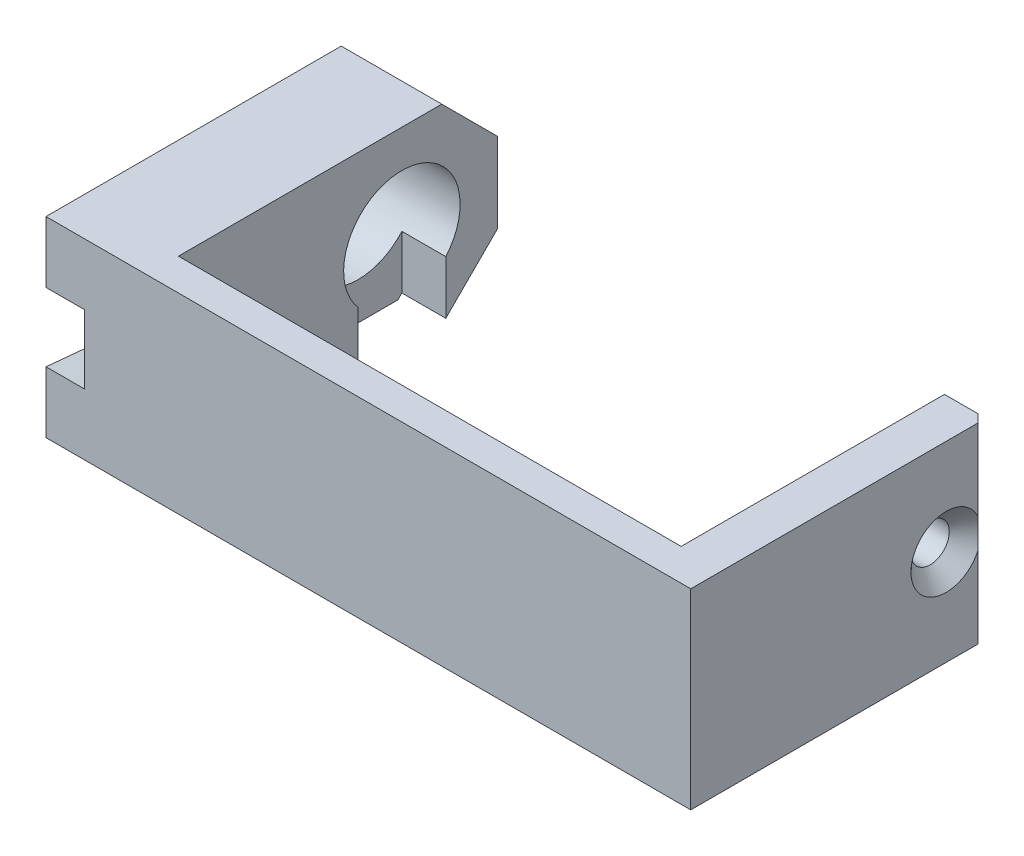
SolidWorks part; units mm, degrees
ref_plane "Front" through (0, 0, 0) normal (0, 0, 1) x (1, 0, 0)
ref_plane "Top" through (0, 0, 0) normal (0, 1, 0) x (1, 0, 0)
ref_plane "Right" through (0, 0, 0) normal (1, 0, 0) x (0, 0, -1)
sketch "Sketch1" plane through (0, 0, 0) normal (0, 0, 1) x (1, 0, 0)
  line L5 (20.2, -6) -> (-20.2, -6)
  line L6 (20.2, -6) -> (20.2, 6)
  line L7 (20.2, 6) -> (-20.2, 6)
  line L8 (-20.2, -6) -> (-20.2, 6)
  line L9 (20.2, -6) -> (-20.2, 6) construction
  line L10 (20.2, 6) -> (-20.2, -6) construction
  point P0 (0, 0)
  dimension "D1" = 40.4
  dimension "D2" = 12
extrude "Boss-Extrude1" add sketch "Sketch1" along normal blind 22 contours L7 L8 L5 L6
sketch "Sketch2" plane through (0, 6, 0) normal (0, 1, 0) x (1, 0, 0)
  line L0 (20.2, 0) -> (-20.2, 0) construction
  line L1 (-13.9, 0) -> (17.6, 0)
  line L2 (-13.9, 0) -> (-13.9, -20)
  line L3 (-13.9, -20) -> (17.6, -20)
  line L4 (17.6, 0) -> (17.6, -20)
  line L5 (-20.2, -22) -> (-20.2, 0) construction
  line L6 (20.2, -22) -> (20.2, 0) construction
  dimension "D1" = 6.3
  dimension "D2" = 31.5
  dimension "D3" = 20
  dimension "D4" = 2.6
extrude "Cut-Extrude1" cut sketch "Sketch2" against normal up to next
sketch "Sketch4" plane through (20.2, 0, 0) normal (1, 0, 0) x (0, 0, -1)
  line L0 (0, -6) -> (0, 6) construction
  circle A0 centre (-6, 0) radius 0.9
  dimension "D1" = 1.8
  dimension "D2" = 6
extrude "Cut-Extrude2" cut sketch "Sketch4" against normal up to next
ref_plane "Plane1" through (0, -36, 0) normal (0, -1, 0) x (-1, 0, 0)
sketch "Sketch5" plane through (-20.2, 0, 0) normal (-1, 0, 0) x (0, 0, 1)
  line L0 (6, 0) -> (22.45, 0) construction
  line L1 (6.3157, 3.3351) -> (22.6196, 1.792) construction
  line L2 (6.3157, -3.3351) -> (22.6196, -1.792) construction
  line L3 (0, -6) -> (0, 6) construction
  line L4 (6.3439, 3.6338) -> (22.6479, 2.0907)
  line L5 (6.3439, -3.6338) -> (22.6479, -2.0907)
  circle A0 centre (6, 0) radius 3.35 construction
  circle A1 centre (22.45, 0) radius 1.8 construction
  arc A2 (6.3157, 3.3351) -> (6.3157, -3.3351) centre (6, 0) ccw construction
  arc A3 (22.6196, 1.792) -> (22.6196, -1.792) centre (22.45, 0) cw construction
  arc A4 (22.6479, 2.0907) -> (22.6479, -2.0907) centre (22.45, 0) cw
  arc A5 (6.3439, 3.6338) -> (6.3439, -3.6338) centre (6, 0) ccw
  point P6 (2.65, 0)
  point P7 (24.25, 0)
  point P13 (0, 0)
  dimension "D1" = 6.7
  dimension "D2" = 3.6
  dimension "D4" = 0.3
  dimension "D3" = 21.6
  dimension "D5" = 6
sketch "Sketch14" plane through (0, 0, 22) normal (0, 0, 1) x (1, 0, 0)
  line L4 (20.2, -6) -> (20.2, 6)
  line L5 (20.2, 6) -> (-20.2, 6)
  line L6 (-20.2, 6) -> (-20.2, -6)
  line L7 (-20.2, -6) -> (20.2, -6)
  line L8 (20.2, -6) -> (20.2, 6)
  line L9 (20.2, 6) -> (-20.2, 6)
  line L10 (-20.2, 6) -> (-20.2, -6)
  line L11 (-20.2, -6) -> (20.2, -6)
  dimension "D1" = 0
chamfer "Chamfer1" distance 3.5 angle 45 4 edges at (-17.05, -6, 0) (-17.05, 6, 0) (18.9, -6, 0) (18.9, 6, 0)
hole_wizard "CSK for M2 Flat Head Machine Screw1" positions "Sketch17" profile "Sketch18" countersink size "M2" standard "ANSI Metric"
sketch "Sketch17" plane through (20.2, 0, 0) normal (1, 0, 0) x (0, 0, -1)
  point P0 (-6, 0)
sketch "Sketch18" plane through (20.2, 0, 6) normal (0, 1, 0) x (0, 0, -1)
  line L0 (0, 0) -> (0, 13.421)
  line L1 (0, 13.421) -> (1.2, 12.7)
  line L2 (1.2, 12.7) -> (1.2, 1)
  line L3 (1.2, 1) -> (2.2, 0)
  line L5 (2.2, 0) -> (0, 0)
  line L6 (-1.2, 1) -> (-2.2, 0) construction
  line L10 (0, 13.421) -> (-1.2, 12.7) construction
  line L11 (0, -6.35) -> (0, 107.95) construction
  dimension "Hole Dia." = 2.4
  dimension "Hole Depth" = 12.7
  dimension "Near C'Sink Dia." = 4.4
  dimension "Near C'Sink Angle" = 90
  dimension "Drill Angle" = 118
chamfer "Chamfer2" distance 4 angle 45 1 edges at (20.2, 0, 0)
ref_plane "Plane10" through (0, 0, 0) normal (0, -1, 0) x (-1, 0, 0)
sketch "Sketch20" plane through (17.6, 0, 0) normal (-1, 0, 0) x (0, 0, 1)
  circle A0 centre (6, 0) radius 2.5
  circle A1 centre (6, 0) radius 1.2
  dimension "D1" = 5
extrude "Boss-Extrude2" add sketch "Sketch20" along normal blind 0.5
extrude "Cut-Extrude3" cut sketch "Sketch5" against normal blind 2.4
sketch "Sketch23" plane through (-17.8, 0, 0) normal (-1, 0, 0) x (0, 0, 1)
  circle A0 centre (6, 0) radius 3.65
  arc A1 (6.3439, 3.6338) -> (6.3439, -3.6338) centre (6, 0) ccw construction
extrude "Cut-Extrude4" cut sketch "Sketch23" against normal blind 22.4
sketch "Sketch24" plane through (0, 0, 0) normal (0, -1, 0) x (-1, 0, 0)
  line L0 (13.9, -2.35) -> (13.9, -9.65) construction
  line L1 (16.65, -8.75) -> (11.15, -8.75)
  line L2 (16.65, -8.75) -> (16.65, -3.25)
  line L3 (16.65, -3.25) -> (11.15, -3.25)
  line L4 (11.15, -8.75) -> (11.15, -3.25)
  line L5 (16.65, -8.75) -> (11.15, -3.25) construction
  line L6 (16.65, -3.25) -> (11.15, -8.75) construction
  point P0 (13.9, -6)
  dimension "D1" = 5.5
extrude "Cut-Extrude5" cut sketch "Sketch24" along normal blind 22.4
